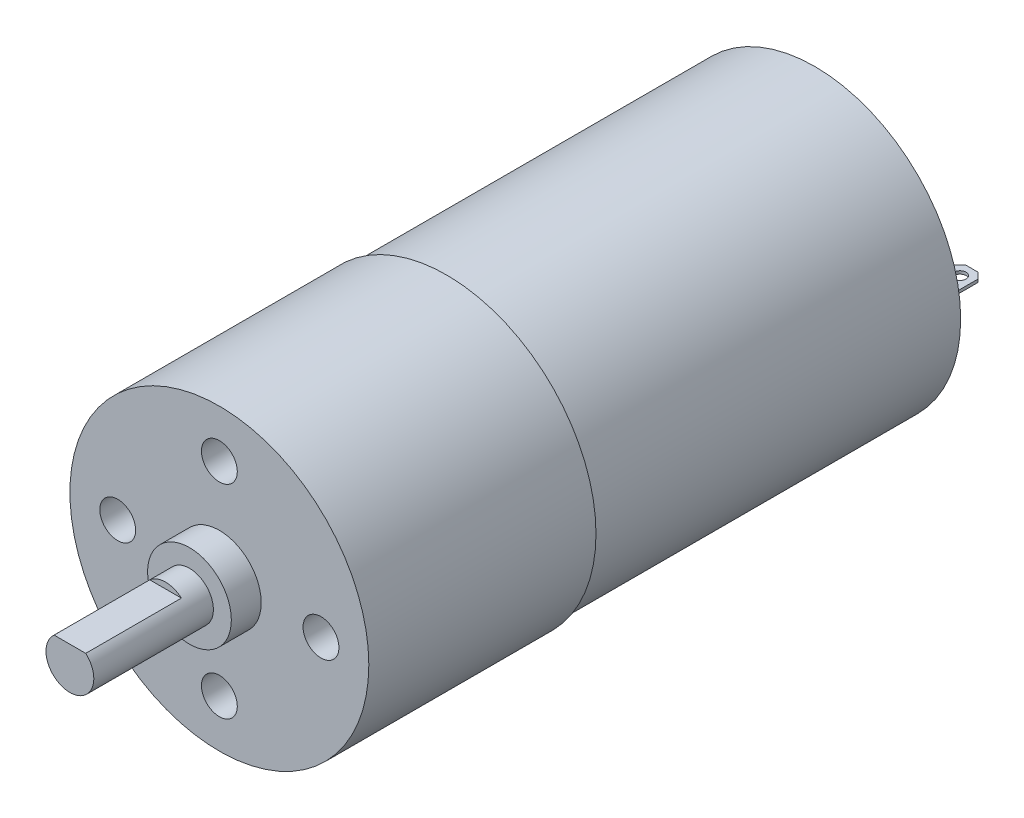
SolidWorks part; units mm, degrees
ref_plane "Front Plane" through (0, 0, 0) normal (0, 0, 1) x (1, 0, 0)
ref_plane "Top Plane" through (0, 0, 0) normal (0, 1, 0) x (1, 0, 0)
ref_plane "Right Plane" through (0, 0, 0) normal (1, 0, 0) x (0, 0, -1)
sketch "Sketch1" plane through (0, 0, 0) normal (0, 0, 1) x (1, 0, 0)
  circle A0 centre (0, 0) radius 12.5
  dimension "D1" = 25
extrude "Boss-Extrude1" add sketch "Sketch1" against normal blind 19
sketch "Sketch2" plane through (0, 0, -19) normal (0, 0, -1) x (-1, 0, 0)
  circle A0 centre (0, 0) radius 12.2
  dimension "D1" = 24.4
extrude "Boss-Extrude2" add sketch "Sketch2" along normal blind 30.8
sketch "Sketch3" plane through (0, 0, 0) normal (0, 0, 1) x (1, 0, 0)
  circle A0 centre (-8.5, 0) radius 1.5
  dimension "D1" = 8.5
extrude "Cut-Extrude1" cut sketch "Sketch3" against normal blind 10
ref_axis "Axis1" through (0, 0, -19) along (0, 0, 1)
pattern_circular "CirPattern1" count 4 every 90 about axis through (0, 0, -19) along (0, 0, 1) of "Cut-Extrude1"
sketch "Sketch4" plane through (0, 0, 0) normal (0, 0, 1) x (1, 0, 0)
  circle A0 centre (0, 0) radius 3.5
  dimension "D1" = 7
extrude "Boss-Extrude3" add sketch "Sketch4" along normal blind 2.5
sketch "Sketch6" plane through (0, 0, 2.5) normal (0, 0, 1) x (1, 0, 0)
  line L0 (-1.3229, 1.5) -> (1.3229, 1.5)
  arc A0 (-1.3229, 1.5) -> (1.3229, 1.5) centre (0, 0) ccw
  dimension "D1" = 4
  dimension "D2" = 1.5
extrude "Boss-Extrude4" add sketch "Sketch6" along normal blind 10
sketch "Sketch7" plane through (0, 0, 2.5) normal (0, 0, 1) x (1, 0, 0)
  circle A0 centre (0, 0) radius 2
extrude "Boss-Extrude5" add sketch "Sketch7" along normal blind 2
sketch "Sketch8" plane through (0, 0, -49.8) normal (0, 0, -1) x (-1, 0, 0)
  line L1 (-10.15, 0.125) -> (-8.15, 0.125)
  line L2 (-10.15, 0.125) -> (-10.15, -0.125)
  line L3 (-10.15, -0.125) -> (-8.15, -0.125)
  line L4 (-8.15, 0.125) -> (-8.15, -0.125)
  dimension "D1" = 2
  dimension "D2" = 0.25
  dimension "D3" = 0.125
  dimension "D4" = 8.15
extrude "Boss-Extrude6" add sketch "Sketch8" along normal blind 4
chamfer "Chamfer1" distance 0.5 angle 45 2 edges at (10.15, 0, -53.8) (8.15, 0, -53.8)
sketch "Sketch10" plane through (0, 0.125, 0) normal (0, 1, 0) x (1, 0, 0)
  line L0 (8.15, 53.3) -> (8.15, 49.8) construction
  line L2 (8.65, 53.8) -> (9.65, 53.8) construction
  circle A0 centre (9.15, 52.8) radius 0.5
  dimension "D3" = 1
  dimension "D1" = 1
  dimension "D2" = 1
extrude "Cut-Extrude2" cut sketch "Sketch10" against normal up to next
pattern_circular "CirPattern2" count 2 every 180 about axis through (0, 0, -19) along (0, 0, 1) of "Cut-Extrude2", "Boss-Extrude6", "Chamfer1"
sketch "Sketch11" plane through (0, 0, -49.8) normal (0, 0, -1) x (-1, 0, 0)
  circle A0 centre (0, 0) radius 3.5
  dimension "D1" = 7
extrude "Boss-Extrude7" add sketch "Sketch11" along normal blind 1.5
fillet "Fillet1" radius 0.25 1 edges at (-3.5, 0, -51.3)
equation "\"D3@Sketch8\"=0.5 * \"D2@Sketch8\""
equation "\"D4@Sketch8\"= (18.3/2) - (\"D1@Sketch8\" /2)"
